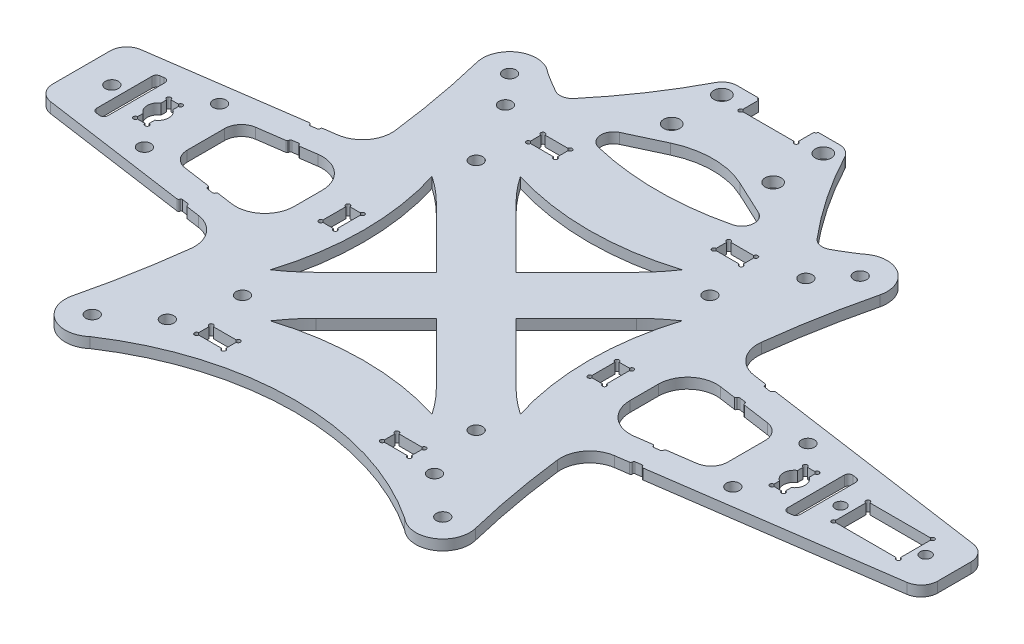
SolidWorks part; units mm, degrees
material "PPS"
ref_plane "前视基准面" through (0, 0, 0) normal (0, 0, 1) x (1, 0, 0)
ref_plane "上视基准面" through (0, 0, 0) normal (0, 1, 0) x (1, 0, 0)
ref_plane "右视基准面" through (0, 0, 0) normal (1, 0, 0) x (0, 0, -1)
sketch "草图1" plane through (0, 0, 0) normal (0, 1, 0) x (1, 0, 0)
  line L3 (-133.7177, 0) -> (146.3754, 0) construction
  line L56 (0, 96.0639) -> (0, -115.1457) construction
  line L65 (-25.5, 41.5) -> (-19, 41.5)
  line L66 (-34, 3.25) -> (-30.5, 3.25)
  line L70 (-34, 3.25) -> (-34, -3.25)
  line L76 (-34, -3.25) -> (-30.5, -3.25)
  line L80 (-30.5, 3.25) -> (-30.5, -3.25)
  line L81 (-25.5, -38) -> (-19, -38)
  line L82 (-25.5, -38) -> (-25.5, -41.5)
  line L83 (-25.5, -41.5) -> (-19, -41.5)
  line L84 (-19, -38) -> (-19, -41.5)
  line L85 (-19, 38) -> (-19, 41.5)
  line L86 (-25.5, 38) -> (-19, 38)
  line L142 (-25.5, 38) -> (-25.5, 41.5)
  line L143 (25.5, 38) -> (25.5, 41.5)
  line L144 (25.5, 38) -> (19, 38)
  line L145 (19, 38) -> (19, 41.5)
  line L146 (19, -38) -> (19, -41.5)
  line L147 (25.5, -41.5) -> (19, -41.5)
  line L148 (25.5, -38) -> (25.5, -41.5)
  line L149 (25.5, -38) -> (19, -38)
  line L150 (30.5, 3.25) -> (30.5, -3.25)
  line L151 (34, -3.25) -> (30.5, -3.25)
  line L152 (34, 3.25) -> (34, -3.25)
  line L153 (34, 3.25) -> (30.5, 3.25)
  line L154 (25.5, 41.5) -> (19, 41.5)
  line L155 (77.65, -2.1518) -> (77.65, -4)
  line L156 (74.85, 4) -> (77.65, 4)
  line L157 (74.85, 4) -> (74.85, 2.1768)
  line L158 (74.85, -4) -> (77.65, -4)
  line L159 (77.65, 4) -> (77.65, 2.1518)
  line L160 (74.85, -2.1768) -> (74.85, -4)
  line L161 (97.5, 7.6653) -> (97.5, -9.1503) construction
  line L162 (89.75, 4.1) -> (105.25, 4.1)
  line L163 (89.75, 4.1) -> (89.75, -4.1)
  line L164 (89.75, -4.1) -> (105.25, -4.1)
  line L165 (105.25, 4.1) -> (105.25, -4.1)
  line L166 (-97.5, 7.6653) -> (-97.5, -9.1503) construction
  line L171 (-74.85, -2.1768) -> (-74.85, -4)
  line L172 (-77.65, 4) -> (-77.65, 2.1518)
  line L173 (-74.85, -4) -> (-77.65, -4)
  line L174 (-74.85, 4) -> (-74.85, 2.1768)
  line L175 (-74.85, 4) -> (-77.65, 4)
  line L176 (-77.65, -2.1518) -> (-77.65, -4)
  line L177 (114.5911, 7.4683) -> (114.5911, -7.4683)
  line L178 (114.5911, 7.4683) -> (43.1936, 17.6463)
  line L179 (114.5911, -7.4683) -> (43.1936, -17.6463)
  line L183 (-23.978, 14.4296) -> (-9.5485, 0)
  line L184 (14.4296, 23.978) -> (0, 9.5485)
  line L185 (-23.978, -14.4296) -> (-9.5485, 0)
  line L186 (-14.4296, 23.978) -> (0, 9.5485)
  line L187 (23.978, -14.4296) -> (9.5485, 0)
  line L188 (23.978, 14.4296) -> (9.5485, 0)
  line L189 (-14.4296, -23.978) -> (0, -9.5485)
  line L190 (14.4296, -23.978) -> (0, -9.5485)
  line L191 (-94.5795, 10.321) -> (-94.5795, -10.321)
  line L192 (-43.1936, 17.6463) -> (-94.5795, 10.321)
  line L193 (-94.5795, -10.321) -> (-43.1936, -17.6463)
  line L195 (-64.75, -7.9571) -> (-64.75, 7.9571)
  line L196 (-64.75, 7.9571) -> (-40.25, 11.4497)
  line L197 (-40.25, 11.4497) -> (-40.25, -11.4497)
  line L198 (-64.75, -7.9571) -> (-40.25, -11.4497)
  line L199 (64.75, 7.9571) -> (40.25, 11.4497)
  line L200 (40.25, 11.4497) -> (40.25, -11.4497)
  line L201 (64.75, -7.9571) -> (40.25, -11.4497)
  line L202 (64.75, 7.9571) -> (64.75, -7.9571)
  line L203 (84.3, 7.5437) -> (81.4, 7.9571)
  line L204 (81.4, 7.9571) -> (81.4, -7.9571)
  line L205 (84.3, -7.5437) -> (81.4, -7.9571)
  line L206 (84.3, 7.5437) -> (84.3, -7.5437)
  line L207 (-84.3, 7.5437) -> (-84.3, -7.5437)
  line L208 (-84.3, -7.5437) -> (-81.4, -7.9571)
  line L209 (-81.4, 7.9571) -> (-81.4, -7.9571)
  line L210 (-84.3, 7.5437) -> (-81.4, 7.9571)
  circle A0 centre (-36, 43) radius 1.55
  circle A1 centre (-32, -42) radius 1.55
  circle A2 centre (32, -42) radius 1.55
  circle A3 centre (36, 43) radius 1.55
  circle A4 centre (42, 50) radius 1.55
  circle A5 centre (42, -50) radius 1.55
  circle A6 centre (-42, -50) radius 1.55
  circle A7 centre (-42, 50) radius 1.55
  arc A8 (74.85, 2.1768) -> (74.85, -2.1768) centre (76.2307, 0) ccw
  arc A9 (77.65, -2.1518) -> (77.65, 2.1518) centre (76.2307, 0) ccw
  circle A10 centre (107.7, 0) radius 1.3
  circle A11 centre (87.3, 0) radius 1.3
  circle A12 centre (-87.3, 0) radius 1.3 construction
  arc A14 (-77.65, -2.1518) -> (-77.65, 2.1518) centre (-76.2307, 0) cw
  arc A15 (-74.85, 2.1768) -> (-74.85, -2.1768) centre (-76.2307, 0) cw
  arc A18 (-37.7098, 54.831) -> (37.7098, 54.831) centre (0, 111.5317) ccw
  arc A20 (48.2756, 48.4632) -> (43.1936, 17.6463) centre (246.1791, 0) ccw
  arc A21 (48.2756, 48.4632) -> (37.7098, 54.831) centre (42, 50) ccw
  arc A22 (-37.7098, -54.831) -> (37.7098, -54.831) centre (0, -111.5317) cw
  arc A23 (48.2756, -48.4632) -> (43.1936, -17.6463) centre (246.1791, 0) cw
  arc A24 (48.2756, -48.4632) -> (37.7098, -54.831) centre (42, -50) cw
  arc A26 (-48.2756, -48.4632) -> (-37.7098, -54.831) centre (-42, -50) ccw
  arc A27 (-48.2756, -48.4632) -> (-43.1936, -17.6463) centre (-246.1791, 0) ccw
  arc A28 (-48.2756, 48.4632) -> (-37.7098, 54.831) centre (-42, 50) cw
  arc A30 (-48.2756, 48.4632) -> (-43.1936, 17.6463) centre (-246.1791, 0) cw
  arc A31 (-23.978, 14.4296) -> (-29.9602, 19.3706) centre (-52.8883, -14.4807) ccw
  arc A32 (-23.978, -14.4296) -> (-29.9602, -19.3706) centre (-52.8883, 14.4807) cw
  arc A33 (-29.9602, -19.3706) -> (-29.9602, 19.3706) centre (-91.9966, 0) ccw
  arc A34 (-14.4296, 23.978) -> (-19.3706, 29.9602) centre (14.4807, 52.8883) cw
  arc A35 (-19.3706, 29.9602) -> (19.3706, 29.9602) centre (0, 91.9966) ccw
  arc A36 (14.4296, 23.978) -> (19.3706, 29.9602) centre (-14.4807, 52.8883) ccw
  arc A37 (23.978, 14.4296) -> (29.9602, 19.3706) centre (52.8883, -14.4807) cw
  arc A38 (29.9602, 19.3706) -> (29.9602, -19.3706) centre (91.9966, 0) ccw
  arc A39 (23.978, -14.4296) -> (29.9602, -19.3706) centre (52.8883, 14.4807) ccw
  arc A40 (14.4296, -23.978) -> (19.3706, -29.9602) centre (-14.4807, -52.8883) cw
  arc A41 (19.3706, -29.9602) -> (-19.3706, -29.9602) centre (0, -91.9966) ccw
  arc A42 (-14.4296, -23.978) -> (-19.3706, -29.9602) centre (14.4807, -52.8883) ccw
  circle A43 centre (70.5, 9) radius 1.55
  circle A44 centre (70.5, -9) radius 1.55
  circle A45 centre (-70.5, -9) radius 1.55
  circle A46 centre (-70.5, 9) radius 1.55
  circle A47 centre (-87.3, 0) radius 1.55
  point P81 (-34, 0)
  point P118 (0, 0)
  point P140 (-40.25, 0)
  point P149 (-64.75, 0)
  dimension "D5" = 38
  dimension "D18" = 8.2
  dimension "D24" = 3.1
  dimension "D6" = 3.1
  dimension "D11" = 50
  dimension "D15" = 74.85
  dimension "D16" = 2.6
  dimension "D17" = 15.5
  dimension "D21" = 3.1
  dimension "D1" = 6.5
  dimension "D2" = 3.5
  dimension "D3" = 30.5
  dimension "D4" = 19
  dimension "D7" = 32
  dimension "D8" = 42
  dimension "D9" = 43
  dimension "D10" = 36
  dimension "D12" = 42
  dimension "D13" = 2.8
  dimension "D14" = 4
  dimension "D19" = 2.45
  dimension "D20" = 97.5
  dimension "D22" = 9
  dimension "D23" = 70.5
  dimension "D25" = 6.55
  dimension "D26" = 5.75
  dimension "D27" = 6.25
  dimension "D28" = 4
  dimension "D29" = 2.45
  dimension "D30" = 3
  dimension "D31" = 3.75
extrude "凸台-拉伸1" add sketch "草图1" along normal blind 2.5
fillet "圆角1" radius 4 8 edges at (114.5911, 1.25, -7.4683) (114.5911, 1.25, 7.4683) (-94.5795, 1.25, 10.321) (-94.5795, 1.25, -10.321) (-64.75, 1.25, 7.9571) (-64.75, 1.25, -7.9571) (64.75, 1.25, 7.9571) (64.75, 1.25, -7.9571)
fillet "圆角2" radius 7 8 edges at (43.1936, 1.25, -17.6463) (43.1936, 1.25, 17.6463) (-43.1936, 1.25, 17.6463) (-43.1936, 1.25, -17.6463) (40.25, 1.25, 11.4497) (40.25, 1.25, -11.4497) (-40.25, 1.25, 11.4497) (-40.25, 1.25, -11.4497)
sketch "草图6" plane through (0, 2.5, 0) normal (0, 1, 0) x (1, 0, 0)
  line L0 (53.296, 16.2062) -> (55.6373, 15.8724)
  line L1 (111.1557, 7.958) -> (49.8638, 16.6954) construction
  line L2 (55.6373, 15.8724) -> (55.2455, 15.2717)
  line L3 (55.2455, 15.2717) -> (53.296, 15.5496)
  line L4 (53.296, 15.5496) -> (53.296, 16.2062)
  line L5 (56.9219, 15.6893) -> (55.9975, 9.2048) construction
  line L6 (61.3145, 8.4469) -> (48.2379, 10.311) construction
  line L7 (56.4597, 12.447) -> (48.7761, 13.5424) construction
  line L8 (54.5046, 10.0742) -> (52.555, 10.3521)
  line L9 (54.7129, 9.3879) -> (54.5046, 10.0742)
  line L10 (52.3716, 9.7217) -> (54.7129, 9.3879)
  line L11 (52.555, 10.3521) -> (52.3716, 9.7217)
  line L12 (0, 0) -> (132.6638, 0) construction
  line L13 (52.555, -10.3521) -> (52.3716, -9.7217)
  line L14 (52.3716, -9.7217) -> (54.7129, -9.3879)
  line L15 (54.7129, -9.3879) -> (54.5046, -10.0742)
  line L16 (54.5046, -10.0742) -> (52.555, -10.3521)
  line L17 (53.296, -15.5496) -> (53.296, -16.2062)
  line L18 (55.2455, -15.2717) -> (53.296, -15.5496)
  line L19 (55.6373, -15.8724) -> (55.2455, -15.2717)
  line L20 (53.296, -16.2062) -> (55.6373, -15.8724)
  line L21 (0, -0.7474) -> (0, 57.4396) construction
  line L22 (-53.296, -16.2062) -> (-55.6373, -15.8724)
  line L23 (-55.6373, -15.8724) -> (-55.2455, -15.2717)
  line L24 (-55.2455, -15.2717) -> (-53.296, -15.5496)
  line L25 (-53.296, -15.5496) -> (-53.296, -16.2062)
  line L26 (-54.5046, -10.0742) -> (-52.555, -10.3521)
  line L27 (-54.7129, -9.3879) -> (-54.5046, -10.0742)
  line L28 (-52.3716, -9.7217) -> (-54.7129, -9.3879)
  line L29 (-52.555, -10.3521) -> (-52.3716, -9.7217)
  line L30 (-52.555, 10.3521) -> (-52.3716, 9.7217)
  line L31 (-52.3716, 9.7217) -> (-54.7129, 9.3879)
  line L32 (-54.7129, 9.3879) -> (-54.5046, 10.0742)
  line L33 (-54.5046, 10.0742) -> (-52.555, 10.3521)
  line L34 (-53.296, 15.5496) -> (-53.296, 16.2062)
  line L35 (-55.2455, 15.2717) -> (-53.296, 15.5496)
  line L36 (-55.6373, 15.8724) -> (-55.2455, 15.2717)
  line L37 (-53.296, 16.2062) -> (-55.6373, 15.8724)
  dimension "D1" = 65
  dimension "D2" = 0.65
extrude "切除-拉伸3" cut sketch "草图6" against normal through all
fillet "圆角5" radius 0.35 32 edges at (-55.6373, 1.25, -15.8724) (-55.2455, 1.25, -15.2717) (-53.296, 1.25, -15.5496) (-53.296, 1.25, -16.2062) (-52.3716, 1.25, 9.7217) (-52.555, 1.25, 10.3521) (-54.5046, 1.25, 10.0742) (-54.7129, 1.25, 9.3879) (-52.3716, 1.25, -9.7217) (-52.555, 1.25, -10.3521) (-54.7129, 1.25, -9.3879) (-54.5046, 1.25, -10.0742) (-53.296, 1.25, 16.2062) (-53.296, 1.25, 15.5496) (-55.2455, 1.25, 15.2717) (-55.6373, 1.25, 15.8724) (55.6373, 1.25, 15.8724) (55.2455, 1.25, 15.2717) (53.296, 1.25, 15.5496) (53.296, 1.25, 16.2062) (54.7129, 1.25, 9.3879) (54.5046, 1.25, 10.0742) (52.555, 1.25, 10.3521) (52.3716, 1.25, 9.7217) (54.7129, 1.25, -9.3879) (54.5046, 1.25, -10.0742) (52.3716, 1.25, -9.7217) (52.555, 1.25, -10.3521) (55.2455, 1.25, -15.2717) (53.296, 1.25, -15.5496) (55.6373, 1.25, -15.8724) (53.296, 1.25, -16.2062)
fillet "圆角4" radius 1 8 edges at (-81.4, 1.25, 7.9571) (-84.3, 1.25, 7.5437) (-84.3, 1.25, -7.5437) (-81.4, 1.25, -7.9571) (81.4, 1.25, 7.9571) (84.3, 1.25, 7.5437) (84.3, 1.25, -7.5437) (81.4, 1.25, -7.9571)
sketch "光流接口-修改" plane through (0, 0, 0) normal (0, 1, 0) x (1, 0, 0)
  line L0 (30.6813, 50.7398) -> (31.1861, 48.4697)
  line L1 (-31.1861, 48.4697) -> (-30.6813, 50.7398)
  line L2 (-6.65, 74.7843) -> (-6.65, 70.0343)
  line L3 (-6.65, 70.0343) -> (-0.15, 70.0343)
  line L4 (-0.15, 70.0343) -> (-0.15, 74.7843) construction
  line L5 (-12.6171, 74.7843) -> (-6.65, 74.7843)
  line L6 (-0.15, 70.0343) -> (0.15, 70.0343)
  line L7 (6.65, 70.0343) -> (0.15, 70.0343)
  line L8 (0.15, 70.0343) -> (0.15, 74.7843) construction
  line L9 (6.65, 74.7843) -> (6.65, 70.0343)
  line L10 (12.6171, 74.7843) -> (6.65, 74.7843)
  line L12 (8.3096, 54.8814) -> (29.4648, 44.9866)
  line L14 (0, -39.4607) -> (0, 39.4607) construction
  line L16 (-8.3096, 54.8814) -> (-29.4648, 44.9866)
  line L17 (-12.6171, 74.7843) -> (12.6171, 74.7843) construction
  arc A6 (15.4956, 72.7963) -> (11.6829, 74.7843) centre (12.15, 71.03) ccw
  arc A7 (-11.6829, 74.7843) -> (-15.4956, 72.7963) centre (-12.15, 71.03) ccw
  arc A8 (-37.7098, 54.831) -> (37.7098, 54.831) centre (0, 111.5317) ccw construction
  circle A38 centre (-12.15, 71.03) radius 1.925
  circle A39 centre (-12.15, 59) radius 1.925
  circle A40 centre (12.15, 59) radius 1.925
  circle A41 centre (12.15, 71.03) radius 1.925
  circle A42 centre (-36, 43) radius 1.55
  circle A43 centre (36, 43) radius 1.55
  arc A44 (-36.5378, 46.9637) -> (-32.3705, 41.3187) centre (-36, 43) ccw
  arc A45 (36.5378, 46.9637) -> (32.3705, 41.3187) centre (36, 43) cw
  arc A46 (32.3705, 41.3187) -> (29.4648, 44.9866) centre (23.2968, 37.1154) ccw
  arc A47 (36.5378, 46.9637) -> (31.1861, 48.4697) centre (39.227, 66.7821) cw
  arc A48 (-8.3096, 54.8814) -> (8.3096, 54.8814) centre (0, 37.1154) cw
  arc A49 (15.4956, 72.7963) -> (30.6813, 50.7398) centre (116.756, 126.2568) ccw
  arc A52 (-15.4956, 72.7963) -> (-30.6813, 50.7398) centre (-116.756, 126.2568) cw
  arc A53 (-36.5378, 46.9637) -> (-31.1861, 48.4697) centre (-39.227, 66.7821) ccw
  arc A54 (-32.3705, 41.3187) -> (-29.4648, 44.9866) centre (-23.2968, 37.1154) cw
  arc A55 (-36.5378, 46.9637) -> (-32.3705, 41.3187) centre (-36, 43) ccw
  circle A56 centre (-36, 43) radius 1.55
  point P10 (0, 74.7843)
  point P11 (-0.15, 37.1154)
  point P13 (0, 0)
  point P15 (28.362, 51.9096)
  point P16 (31.1861, 48.4697)
  point P17 (28.9381, 52.3079)
  point P18 (30.6813, 50.7398)
  dimension "D4" = 3.85
  dimension "D1" = 12.03
  dimension "D2" = 24.3
  dimension "D3" = 59
  dimension "D5" = 5.5
  dimension "D6" = 6.5
  dimension "D7" = 4.75
extrude "凸台-拉伸2" add sketch "光流接口-修改" along normal up to surface (2.5 mm away) from surface contours A48 L14 L17 A52 L1 A53 A44 A54 L16 A42 A39 A38 | L14 A48 L12 A46 A45 A47 L0 A49 L17 A40 A41 A43 region at (0, 0, -58.3977) up to face at (53.4999, 2.5, 0) starting at face at (53.4999, 0, 0)
sketch "草图10" plane through (0, 0, 0) normal (0, 1, 0) x (1, 0, 0)
  line L0 (0, 0) -> (0, -66.7571) construction
  line L1 (-6.65, 70.0343) -> (6.65, 70.0343) construction
  circle A0 centre (-77.65, 4) radius 0.5
  circle A1 centre (-74.85, 4) radius 0.5
  circle A2 centre (-77.65, -4) radius 0.5
  circle A3 centre (-74.85, -4) radius 0.5
  circle A4 centre (-25.5, 41.5) radius 0.5
  circle A5 centre (-19, 41.5) radius 0.5
  circle A6 centre (-25.5, 38) radius 0.5
  circle A7 centre (-19, 38) radius 0.5
  circle A8 centre (-34, 3.25) radius 0.5
  circle A9 centre (-30.5, 3.25) radius 0.5
  circle A10 centre (-34, -3.25) radius 0.5
  circle A11 centre (-30.5, -3.25) radius 0.5
  circle A12 centre (-25.5, -38) radius 0.5
  circle A13 centre (-19, -38) radius 0.5
  circle A14 centre (-25.5, -41.5) radius 0.5
  circle A15 centre (-19, -41.5) radius 0.5
  circle A16 centre (19, -41.5) radius 0.5
  circle A17 centre (25.5, -41.5) radius 0.5
  circle A18 centre (19, -38) radius 0.5
  circle A19 centre (25.5, -38) radius 0.5
  circle A20 centre (30.5, -3.25) radius 0.5
  circle A21 centre (34, -3.25) radius 0.5
  circle A22 centre (30.5, 3.25) radius 0.5
  circle A23 centre (34, 3.25) radius 0.5
  circle A24 centre (19, 38) radius 0.5
  circle A25 centre (25.5, 38) radius 0.5
  circle A26 centre (19, 41.5) radius 0.5
  circle A27 centre (25.5, 41.5) radius 0.5
  circle A28 centre (74.85, -4) radius 0.5
  circle A29 centre (77.65, -4) radius 0.5
  circle A30 centre (74.85, 4) radius 0.5
  circle A31 centre (77.65, 4) radius 0.5
  circle A32 centre (89.75, 4.1) radius 0.5
  circle A33 centre (105.25, 4.1) radius 0.5
  circle A34 centre (89.75, -4.1) radius 0.5
  circle A35 centre (105.25, -4.1) radius 0.5
  circle A37 centre (-6.65, 70.0343) radius 0.5
  circle A38 centre (6.65, 70.0343) radius 0.5
  circle A39 centre (-6.65, 74.7843) radius 0.5
  circle A40 centre (6.65, 74.7843) radius 0.5
  dimension "D1" = 1
extrude "切除-拉伸6" cut sketch "草图10" along normal through all
sketch "草图11" plane through (0, 0, 0) normal (0, -1, 0) x (1, 0, 0)
  line L0 (0, 0) -> (0, -50000) construction
  line L1 (0, 0) -> (-50000, 0) construction
  circle A0 centre (28, -28) radius 1.55
  circle A1 centre (-28, -28) radius 1.55
  circle A2 centre (-28, 28) radius 1.55
  circle A3 centre (28, 28) radius 1.55
  dimension "D1" = 3.1
  dimension "D2" = 28
  dimension "D3" = 28
  dimension "D4" = 4
extrude "保护壳内部的安装孔-先用来连接电池板" cut sketch "草图11" against normal through all
fillet "圆角6" radius 3 4 edges at (-30.6813, 1.25, -50.7398) (30.6813, 1.25, -50.7398) (-23.6873, 1.25, -47.6889) (23.6873, 1.25, -47.6889)
